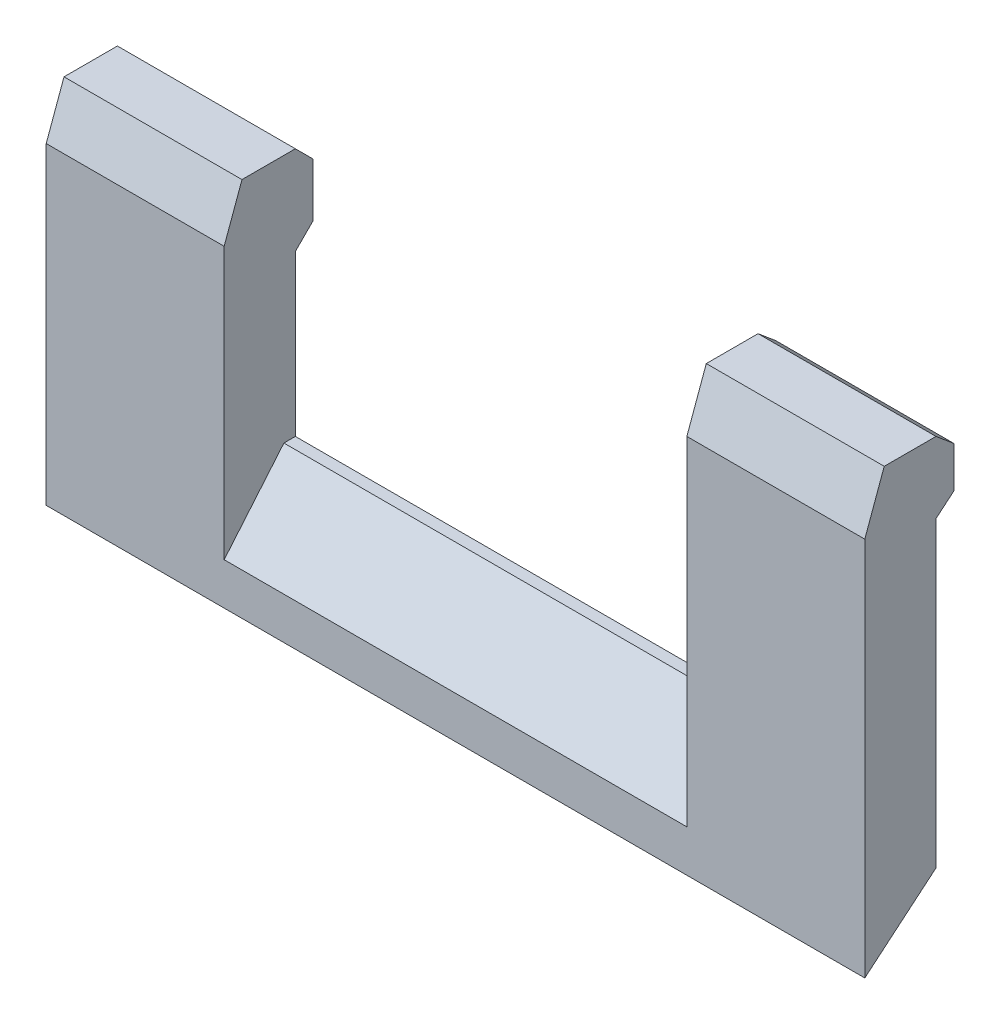
SolidWorks part; units mm, degrees
ref_plane "Front" through (0, 0, 0) normal (0, 0, 1) x (1, 0, 0)
ref_plane "Top" through (0, 0, 0) normal (0, 1, 0) x (1, 0, 0)
ref_plane "Right" through (0, 0, 0) normal (1, 0, 0) x (0, 0, -1)
sketch "草图1" plane through (0, 0, 0) normal (0, 1, 0) x (1, 0, 0)
  line L1 (11.5, -1) -> (-11.5, -1)
  line L2 (11.5, -1) -> (11.5, 1)
  line L3 (11.5, 1) -> (-11.5, 1)
  line L4 (-11.5, -1) -> (-11.5, 1)
  line L5 (11.5, -1) -> (-11.5, 1) construction
  line L6 (11.5, 1) -> (-11.5, -1) construction
  point P0 (0, 0)
  dimension "D1" = 23
  dimension "D2" = 2
extrude "凸台-拉伸1" add sketch "草图1" along normal blind 5
chamfer "倒角1" distance 2 angle 40 1 edges at (0, 5, 1) first distance on face at (0, 2.5, 1)
sketch "草图2" plane through (0, 0, 0) normal (0, 1, 0) x (1, 0, 0)
  line L0 (11.5, -1) -> (-11.5, -1) construction
  line L1 (-11.5, 1) -> (-6.5, 1)
  line L2 (-11.5, 1) -> (-11.5, -1)
  line L3 (-11.5, -1) -> (-6.5, -1)
  line L4 (-6.5, 1) -> (-6.5, -1)
  line L5 (0, 8.5488) -> (0, -7.6111) construction
  line L10 (6.5, 1) -> (6.5, -1)
  line L11 (11.5, -1) -> (6.5, -1)
  line L12 (11.5, 1) -> (11.5, -1)
  line L13 (11.5, 1) -> (6.5, 1)
  dimension "D1" = 5
  dimension "D2" = 2
  dimension "D3" = 13
extrude "凸台-拉伸2" add sketch "草图2" along normal blind 14
chamfer "倒角2" [suppressed] distance 2 angle 45
sketch "草图3" plane through (11.5, 0, 0) normal (1, 0, 0) x (0, 0, -1)
  line L0 (-1, 1.8218) -> (1, 3.5)
  line L1 (-1, 14) -> (-1, 0) construction
  line L2 (1, 14) -> (1, 0) construction
  line L3 (1, 3.5) -> (1, 0)
  line L4 (1, 0) -> (-1, 0)
  line L5 (-1, 0) -> (-1, 1.8218)
  dimension "D1" = 50
  dimension "D2" = 3.5
extrude "切除-拉伸1" cut sketch "草图3" against normal through all
sketch "草图4" plane through (0, 0, -1) normal (0, 0, -1) x (-1, 0, 0)
  line L0 (-6.5, 14) -> (-6.5, 5) construction
  line L1 (-11.5, 14) -> (-6.5, 14)
  line L2 (-11.5, 14) -> (-11.5, 12)
  line L3 (-11.5, 12) -> (-6.5, 12)
  line L4 (-6.5, 14) -> (-6.5, 12)
  line L5 (0, 19.4539) -> (0, -5.5148) construction
  dimension "D1" = 2
extrude "凸台-拉伸3" add sketch "草图4" along normal blind 0.5
chamfer "倒角3" distance 0.5 angle 40 2 edges at (9, 12, -1.5) (9, 14, -1.5) first distance on face at (9, 12, -1.25) first distance on face at (9, 14, -0.25)
sketch "草图5" plane through (0, 0, -1) normal (0, 0, -1) x (-1, 0, 0)
  line L0 (11.5, 14) -> (11.5, 3.5) construction
  line L1 (6.5, 14) -> (11.5, 14)
  line L2 (6.5, 14) -> (6.5, 12)
  line L3 (6.5, 12) -> (11.5, 12)
  line L4 (11.5, 14) -> (11.5, 12)
  dimension "D1" = 2
extrude "切除-拉伸2" cut sketch "草图5" against normal through all
chamfer "倒角4" distance 1.5 angle 20 1 edges at (9, 14, 1) first distance on face at (0, 7.7055, 1)
sketch "草图6" plane through (0, 0, -1) normal (0, 0, -1) x (-1, 0, 0)
  line L0 (11.5, 12) -> (11.5, 3.5) construction
  line L1 (6.5, 12) -> (11.5, 12)
  line L2 (6.5, 12) -> (6.5, 10)
  line L3 (6.5, 10) -> (11.5, 10)
  line L4 (11.5, 12) -> (11.5, 10)
  dimension "D1" = 2
extrude "凸台-拉伸4" add sketch "草图6" along normal blind 0.5
chamfer "倒角5" distance 0.5 angle 45 2 edges at (-9, 10, -1) (-9, 12, -1.5)
chamfer "倒角6" distance 0.5 angle 70 1 edges at (-9, 12, 1) first distance on face at (-9, 12, 0)
